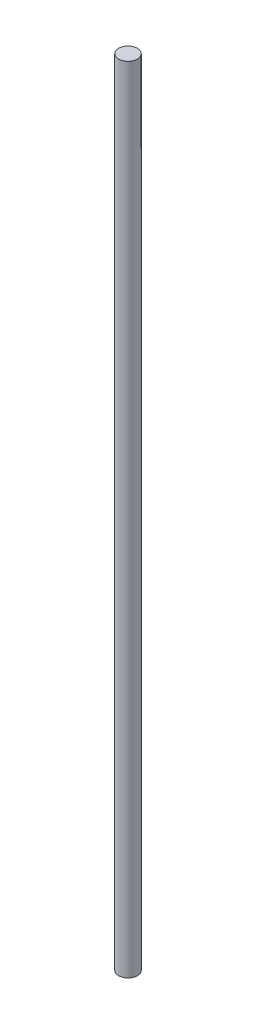
SolidWorks part; units mm, degrees
ref_plane "Front Plane" through (0, 0, 0) normal (0, 0, 1) x (1, 0, 0)
ref_plane "Top Plane" through (0, 0, 0) normal (0, 1, 0) x (1, 0, 0)
ref_plane "Right Plane" through (0, 0, 0) normal (1, 0, 0) x (0, 0, -1)
sketch "Sketch1" plane through (0, 0, 0) normal (0, 1, 0) x (1, 0, 0)
  circle A0 centre (0, 0) radius 3
  dimension "D1" = 6
extrude "Boss-Extrude1" add sketch "Sketch1" along normal blind 254
